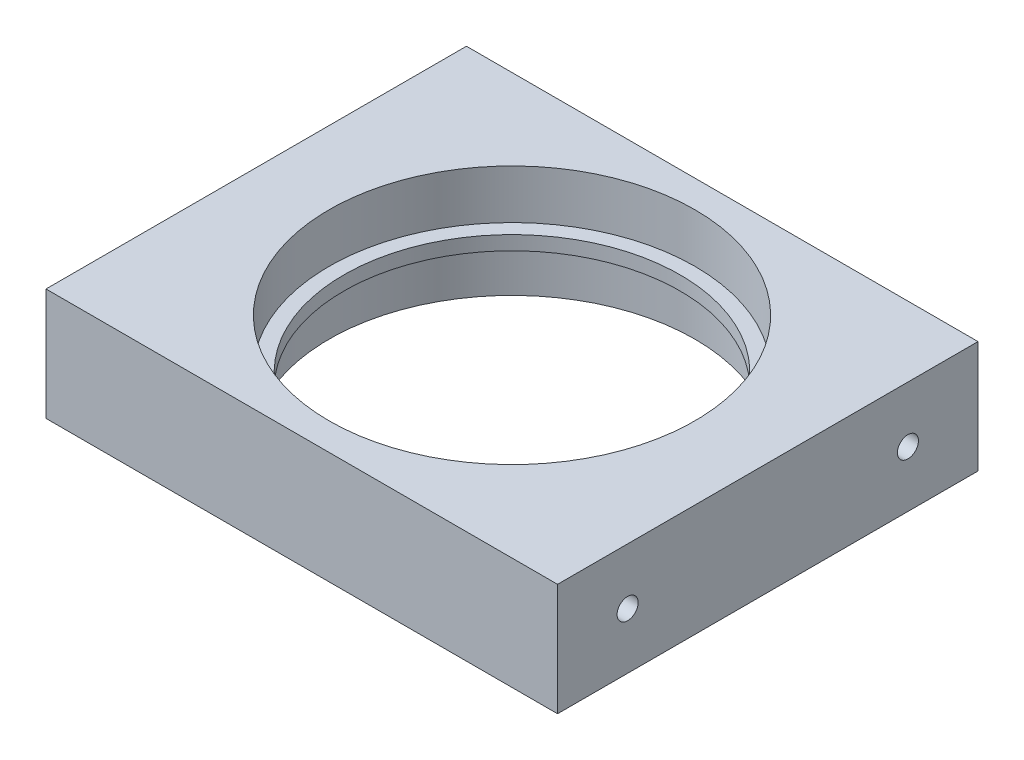
SolidWorks part; units mm, degrees
ref_plane "Front Plane" through (0, 0, 0) normal (0, 0, 1) x (1, 0, 0)
ref_plane "Top Plane" through (0, 0, 0) normal (0, 1, 0) x (1, 0, 0)
ref_plane "Right Plane" through (0, 0, 0) normal (1, 0, 0) x (0, 0, -1)
sketch "Sketch1" plane through (0, 0, 0) normal (0, 1, 0) x (1, 0, 0)
  line L1 (0, 0) -> (73, 0)
  line L2 (0, 0) -> (0, 60)
  line L3 (0, 60) -> (73, 60)
  line L4 (73, 0) -> (73, 60)
  circle A0 centre (36.5, 30) radius 26.1
  point P7 (36.5, 60)
  point P8 (0, 0)
  point P9 (0, 30)
  dimension "D3" = 52.2
  dimension "D1" = 73
  dimension "D2" = 60
extrude "Boss-Extrude1" add sketch "Sketch1" along normal blind 16
sketch "Sketch3" plane through (0, 16, 0) normal (0, 1, 0) x (1, 0, 0)
  circle A0 centre (36.5, 30) radius 24
  circle A1 centre (36.5, 30) radius 26.1 construction
  circle A2 centre (36.5, 30) radius 26.1
  dimension "D1" = 48
extrude "Boss-Extrude2" add sketch "Sketch3" against normal blind 2 from offset 7 offset against normal yes
sketch "Sketch2" plane through (73, 0, 0) normal (1, 0, 0) x (0, 0, -1)
  line L0 (0, 16) -> (0, 0) construction
  line L1 (60, 16) -> (60, 0) construction
  circle A0 centre (10, 8) radius 1.5
  circle A1 centre (50, 8) radius 1.5
  point P6 (0, 8)
  point P7 (0, 0)
  dimension "D3" = 3
  dimension "D1" = 10
  dimension "D2" = 10
extrude "Cut-Extrude1" cut sketch "Sketch2" against normal blind 15
extrude "Cut-Extrude2" cut sketch "Sketch2<2>" along normal blind 15 from surface starting at face at (0, 8, -30)
sketch "Sketch2<2>" plane through (73, 0, 0) normal (1, 0, 0) x (0, 0, -1) same geometry as "Sketch2"
